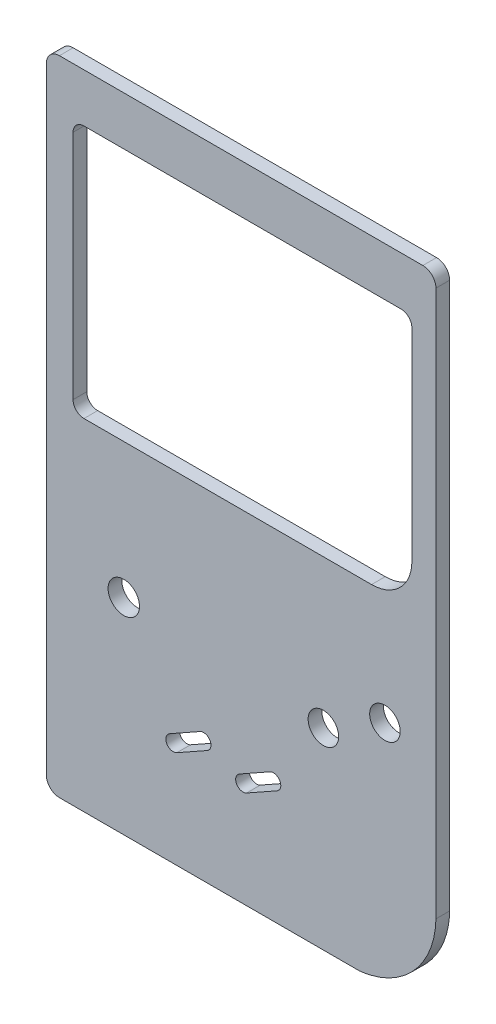
SolidWorks part; units mm, degrees
ref_plane "Front Plane" through (0, 0, 0) normal (0, 0, 1) x (1, 0, 0)
ref_plane "Top Plane" through (0, 0, 0) normal (0, 1, 0) x (1, 0, 0)
ref_plane "Right Plane" through (0, 0, 0) normal (1, 0, 0) x (0, 0, -1)
sketch "Sketch1" plane through (0, 0, 0) normal (0, 0, 1) x (1, 0, 0)
  line L1 (-26.2308, 73.6471) -> (38.6518, 73.6471)
  line L3 (-44.6471, -70.649) -> (-44.6471, 70.649)
  line L5 (27.0934, -73.6471) -> (-41.649, -73.6471)
  line L7 (-24.0867, 73.6955) -> (-35.6911, 73.6955)
  line L15 (-16.3293, -29.1587) -> (-16.3293, -23.8757)
  line L19 (44.6471, 67.6705) -> (44.6471, -53.896)
  line L20 (-0.4012, -48.3225) -> (6.5714, -44.4005)
  line L21 (8.2266, -47.343) -> (1.254, -51.2651)
  line L22 (-44.6471, 73.6471) -> (44.6471, 73.6471)
  line L23 (44.6471, 73.6471) -> (44.6471, -73.6471)
  line L24 (44.6471, -73.6471) -> (-44.6471, -73.6471)
  line L25 (-44.6471, -73.6471) -> (-44.6471, 73.6471)
  line L26 (-25.1679, 56.2163) -> (-25.1679, 10.288)
  line L27 (-25.1679, 10.288) -> (24.9222, 10.288)
  line L28 (24.9222, 10.288) -> (24.9222, 56.2163)
  line L29 (24.9222, 56.2163) -> (-25.1679, 56.2163)
  line L34 (36.6393, 62.5051) -> (-36.0272, 62.5051)
  line L35 (-38.5272, 60.0051) -> (-38.5272, 6.9331)
  line L36 (-36.0272, 4.4331) -> (29.8893, 4.4331)
  line L37 (39.1393, 13.6831) -> (39.1393, 60.0051)
  line L38 (-16.4012, -48.3225) -> (-9.4286, -44.4005)
  line L39 (-7.7734, -47.343) -> (-14.746, -51.2651)
  line L41 (44.6471, 70.649) -> (44.6471, 67.6705)
  line L43 (38.6518, 73.6471) -> (41.649, 73.6471)
  line L45 (-41.649, 73.6471) -> (-26.2308, 73.6471)
  line L150 (42.2525, -55.0539) -> (42.2511, -54.9499)
  circle A0 centre (34.1495, 24.0914) radius 10.7
  circle A2 centre (-26.9008, -26.5172) radius 3.6
  arc A3 (8.2266, -47.343) -> (6.5714, -44.4005) centre (7.399, -45.8717) ccw
  arc A6 (-16.4012, -48.3225) -> (-14.746, -51.2651) centre (-15.5736, -49.7938) ccw
  arc A7 (-7.7734, -47.343) -> (-9.4286, -44.4005) centre (-8.601, -45.8717) ccw
  circle A15 centre (18.8495, -29.5462) radius 3.5
  circle A16 centre (32.9602, -21.4767) radius 3.5
  arc A17 (-0.4012, -48.3225) -> (1.254, -51.2651) centre (0.4264, -49.7938) ccw
  circle A19 centre (-32.9539, 40.3411) radius 4.5
  arc A24 (39.1393, 60.0051) -> (36.6393, 62.5051) centre (36.6393, 60.0051) ccw
  arc A25 (-36.0272, 62.5051) -> (-38.5272, 60.0051) centre (-36.0272, 60.0051) ccw
  arc A26 (-38.5272, 6.9331) -> (-36.0272, 4.4331) centre (-36.0272, 6.9331) ccw
  arc A27 (29.8893, 4.4331) -> (39.1393, 13.6831) centre (29.8893, 13.6831) ccw
  ellipse E3 centre (-41.649, -70.649) end of major axis (-39.5276, -72.7703) minor radius 2.9963 (-44.6471, -70.649) -> (-41.649, -73.6471) ccw
  ellipse E5 centre (41.649, 70.649) end of major axis (39.5276, 72.7703) minor radius 2.9963 (44.6471, 70.649) -> (41.649, 73.6471) ccw
  ellipse E7 centre (-41.649, 70.649) end of major axis (-43.7703, 68.5276) minor radius 2.9963 (-41.649, 73.6471) -> (-44.6471, 70.649) ccw
  spline S1 degree 3 poles (44.6485, -54) (44.663, -55.258) (44.5568, -56.5068) (44.2157, -58.3662) (44.0715, -58.9837) (43.7192, -60.2138) (43.5128, -60.8202) (42.8075, -62.6008) (42.2221, -63.7422) (41.3373, -65.1085) (41.1525, -65.3788) (40.7717, -65.907) (40.5751, -66.1657) (39.9672, -66.9256) (39.1083, -67.8961) (38.1523, -68.7812) (37.1464, -69.6222) (36.6152, -70.0225) (34.9811, -71.1285) (33.8311, -71.748) (32.3187, -72.3766) (32.0124, -72.495) (31.3922, -72.7168) (31.0776, -72.8204) (30.1333, -73.105) (29.5001, -73.2613) (27.5898, -73.6337) (26.302, -73.7542) (25, -73.7456) knots 0 0 0 0 0.125 0.125 0.1875 0.1875 0.25 0.25 0.375 0.375 0.40625 0.40625 0.4375 0.4375 0.5 0.5625 0.5625 0.625 0.625 0.75 0.75 0.78125 0.78125 0.8125 0.8125 0.875 0.875 1 1 1 1
  point P31 (0, 0)
  dimension "D4" = 21.4
  dimension "D8" = 7
  dimension "D11" = 9
  dimension "D12" = 7.2
  dimension "D1" = 10.4977
  dimension "D2" = 89.2943
  dimension "D3" = 147.2943
  dimension "D5" = 25.9097
  dimension "D6" = 8.0696
  dimension "D7" = 14.1107
  dimension "D9" = 7.7861
  dimension "D10" = 22.1641
  dimension "D13" = 10.5715
extrude "Boss-Extrude1" add sketch "Sketch1" along normal blind 3.14 contours S1 L23 L19 A0 L37 A27 L36 A26 L35 A25 L34 A24 E5 L22 L1 E7 L3 E3 L5 A17 L20 A3 L21 A16 A15 A7 L39 A6 L38 A2 | L23 A0 L37 region at (-0.9227, -16.9165, 0) region at (41.4616, 24.0914, 0)
